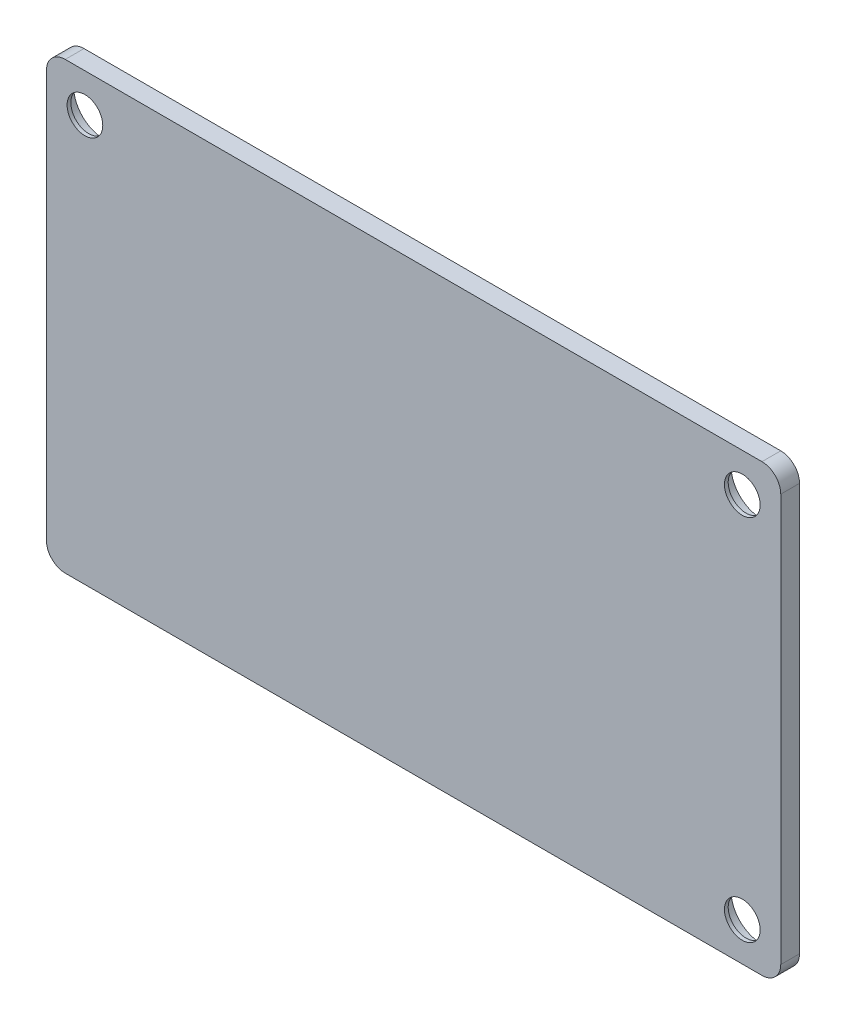
SolidWorks part; units mm, degrees
ref_plane "Front Plane" through (0, 0, 0) normal (0, 0, 1) x (1, 0, 0)
ref_plane "Top Plane" through (0, 0, 0) normal (0, 1, 0) x (1, 0, 0)
ref_plane "Right Plane" through (0, 0, 0) normal (1, 0, 0) x (0, 0, -1)
sketch "Sketch1" plane through (0, 0, 0) normal (0, 0, 1) x (1, 0, 0)
  line L0 (2.3442, 0) -> (2.3442, 34.5863) construction
  line L8 (-48.4558, 0) -> (53.1442, 0) construction
  line L10 (2.3442, 34.5863) -> (2.3442, -34.5863) construction
  line L18 (-47.3066, 24.8858) -> (-47.3066, 30.0866)
  line L19 (-47.3066, 30.0866) -> (-42.1058, 30.0866)
  line L20 (46.7942, 30.0866) -> (-42.1058, 30.0866)
  line L21 (51.995, 24.8858) -> (51.995, -24.8858)
  line L22 (-47.3066, 24.8858) -> (-47.3066, -24.8858)
  line L23 (46.7942, -30.0866) -> (-42.1058, -30.0866)
  line L27 (46.7942, -30.0866) -> (51.995, -30.0866)
  line L28 (51.995, -30.0866) -> (51.995, -24.8858)
  line L33 (51.995, 30.0866) -> (46.7942, 30.0866)
  line L34 (51.995, 24.8858) -> (51.995, 30.0866)
  line L37 (-47.3066, -30.0866) -> (-42.1058, -30.0866)
  line L38 (-47.3066, -24.8858) -> (-47.3066, -30.0866)
  line L39 (51.995, -30.0866) -> (-47.3066, -30.0866)
  line L40 (51.995, -30.0866) -> (51.995, 30.0866)
  line L41 (51.995, 30.0866) -> (-47.3066, 30.0866)
  line L42 (-47.3066, -30.0866) -> (-47.3066, 30.0866)
  circle A0 centre (-42.1058, 24.8858) radius 2.413
  arc A1 (-47.3066, 24.8858) -> (-42.1058, 30.0866) centre (-42.1058, 24.8858) cw construction
  arc A2 (46.7942, 30.0866) -> (51.995, 24.8858) centre (46.7942, 24.8858) cw construction
  circle A5 centre (46.7942, 24.8858) radius 2.413
  circle A13 centre (-42.1058, 24.8858) radius 4.056
  circle A14 centre (46.7942, 24.8858) radius 4.056
  circle A16 centre (46.7942, -24.8858) radius 4.056
  circle A17 centre (46.7942, -24.8858) radius 2.413
  point P0 (2.3442, 0)
  point P5 (2.3442, 0)
  point P39 (2.3442, 24.8858)
  point P41 (2.3442, 30.0866)
  point P45 (-47.3066, 0)
  point P48 (51.995, 0)
  point P53 (-38.7198, 30.216)
  point P56 (46.7942, 0)
  point P61 (-42.1058, 0)
  dimension "D1" = 4.826
extrude "Boss-Extrude1" add sketch "Sketch1" along normal blind 2.54 contours L22 L38 L37 L23 L27 L28 L21 L34 L33 L20 L19 L18 A14 A13 | A13 A0 | A14 A5 | A16 A17 | A5 | A0 region at (1.9495, -0.221, 0) region at (-46.0471, 24.8858, 0) region at (42.8529, 24.8858, 0) region at (42.8529, -24.8858, 0)
extrude "Cut-Extrude1" cut sketch "Sketch1<3>" along normal blind 2.54 contours A5 | A0 | A17 region at (-42.1058, 24.8858, 0) region at (46.7942, 24.8858, 0)
sketch "Sketch1<3>" plane through (0, 0, 0) normal (0, 0, 1) x (1, 0, 0) same geometry as "Sketch1"
extrude "Cut-Extrude2" cut sketch "Sketch1<4>" along normal blind 2.032 contours A14 A5 | A13 A0 | A16 A17 region at (-46.0471, 24.8858, 0) region at (42.8529, 24.8858, 0) region at (42.8529, -24.8858, 0)
sketch "Sketch1<4>" plane through (0, 0, 0) normal (0, 0, 1) x (1, 0, 0) same geometry as "Sketch1"
fillet "Fillet1" radius 2.54 4 edges at (-47.3066, 30.0866, 1.27) (-47.3066, -30.0866, 1.27) (51.995, -30.0866, 1.27) (51.995, 30.0866, 1.27)
